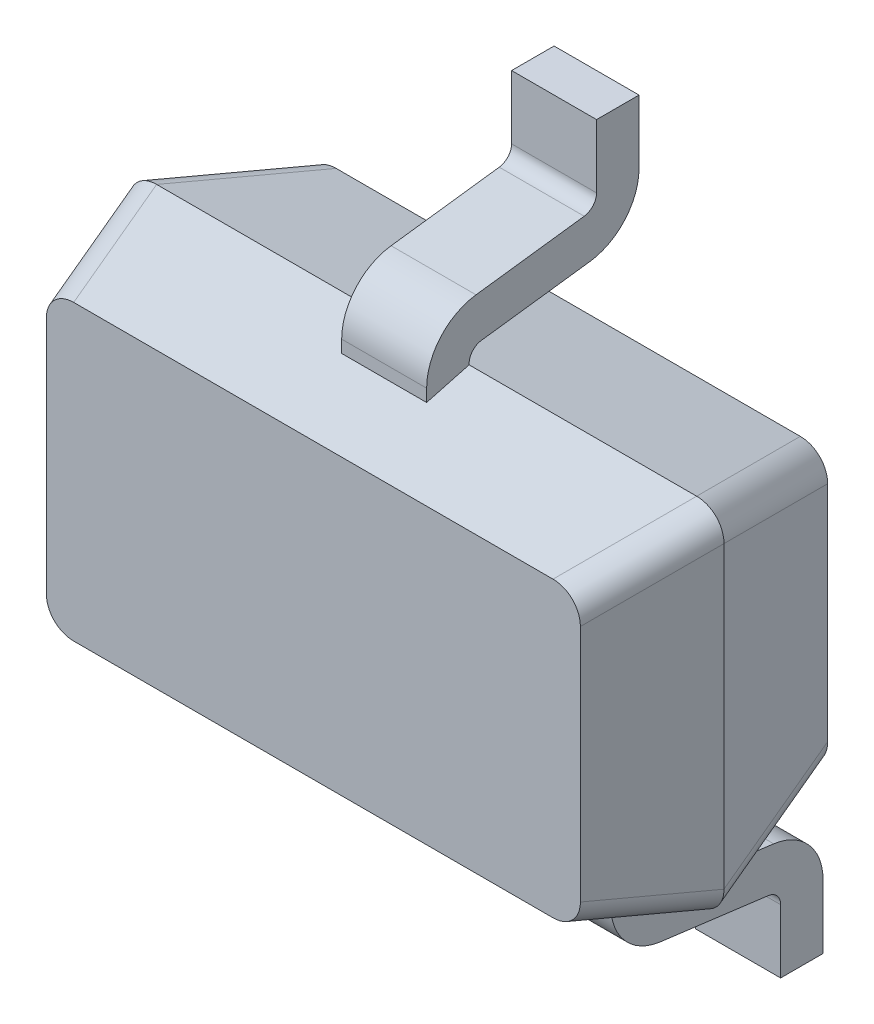
SolidWorks part; units mm, degrees
note: The reader was unsure of these and kept them because the rebuilt part matched: shared geometry of "Эскиз2<4>".
ref_plane "Спереди" through (0, 0, 0) normal (0, 0, 1) x (1, 0, 0)
ref_plane "Сверху" through (0, 0, 0) normal (0, 1, 0) x (1, 0, 0)
ref_plane "Справа" through (0, 0, 0) normal (1, 0, 0) x (0, 0, -1)
sketch "Эскиз1" plane through (0, 0, 0) normal (0, 0, 1) x (1, 0, 0)
  line L1 (-1.05, 0.625) -> (1.05, 0.625)
  line L2 (-1.05, 0.625) -> (-1.05, -0.625)
  line L3 (-1.05, -0.625) -> (1.05, -0.625)
  line L4 (1.05, 0.625) -> (1.05, -0.625)
  point P0 (0, 0)
extrude "Вытянуть1" add sketch "Эскиз1" along normal blind 0.4 draft 15 and the other way blind 0.5 draft 15 from offset 0.6
sketch "Эскиз2" plane through (0, 0, 0) normal (1, 0, 0) x (0, 0, -1)
  line L0 (-0.15, -1.15) -> (0, -1.15)
  line L1 (0, -1.15) -> (0, -0.9259)
  line L2 (-0.75, -0.55) -> (-0.75, -0.6286)
  line L3 (-0.6, -0.6286) -> (-0.6, -0.55)
  line L4 (-0.5564, -0.6782) -> (-0.1744, -0.7275)
  line L5 (-0.15, -1.15) -> (-0.15, -0.9259)
  line L6 (-0.5756, -0.827) -> (-0.1936, -0.8763)
  line L7 (-0.6, -0.625) -> (-0.6, 0.625) construction
  line L8 (-0.6, -0.55) -> (-0.75, -0.55)
  line L9 (0.1932, 0) -> (-1.2427, 0) construction
  line L10 (-0.6, 0.55) -> (-0.75, 0.55)
  line L11 (-0.5756, 0.827) -> (-0.1936, 0.8763)
  line L12 (-0.15, 1.15) -> (-0.15, 0.9259)
  line L13 (-0.5564, 0.6782) -> (-0.1744, 0.7275)
  line L14 (-0.6, 0.6286) -> (-0.6, 0.55)
  line L15 (-0.75, 0.55) -> (-0.75, 0.6286)
  line L16 (0, 1.15) -> (0, 0.9259)
  line L17 (-0.15, 1.15) -> (0, 1.15)
  arc A0 (-0.1936, -0.8763) -> (-0.15, -0.9259) centre (-0.2, -0.9259) cw
  arc A1 (0, -0.9259) -> (-0.1744, -0.7275) centre (-0.2, -0.9259) ccw
  arc A2 (-0.5756, -0.827) -> (-0.75, -0.6286) centre (-0.55, -0.6286) cw
  arc A3 (-0.6, -0.6286) -> (-0.5564, -0.6782) centre (-0.55, -0.6286) ccw
  arc A4 (-0.6, 0.6286) -> (-0.5564, 0.6782) centre (-0.55, 0.6286) cw
  arc A5 (-0.5756, 0.827) -> (-0.75, 0.6286) centre (-0.55, 0.6286) ccw
  arc A6 (0, 0.9259) -> (-0.1744, 0.7275) centre (-0.2, 0.9259) cw
  arc A7 (-0.1936, 0.8763) -> (-0.15, 0.9259) centre (-0.2, 0.9259) ccw
extrude "Вытянуть4" add sketch "Эскиз2" along normal blind 0.3 from offset 0.15 contours L13 A6 L16 L17 L12 A7 L11 A5 L15 L10 L14 A4 offset against normal yes
extrude "Вытянуть5" add sketch "Эскиз2<4>" along normal blind 0.15 and the other way blind 0.15 from offset 0.65 contours A3 L3 L8 L2 A2 L6 A0 L5 L0 L1 A1 L4
sketch "Эскиз2<4>" plane through (0, 0, 0) normal (1, 0, 0) x (0, 0, -1) same geometry as "Эскиз2"
pattern_linear "Линейный массив2" count 2 spacing 1.3 along (-1, 0, 0) of "Вытянуть5"
fillet "Скругление3" radius 0.1 8 edges at (0.9964, -0.5714, 0.8) (0.9964, 0.5714, 0.8) (-0.9964, 0.5714, 0.8) (-0.9964, -0.5714, 0.8) (0.983, -0.558, 0.35) (-0.983, -0.558, 0.35) (-0.983, 0.558, 0.35) (0.983, 0.558, 0.35)
